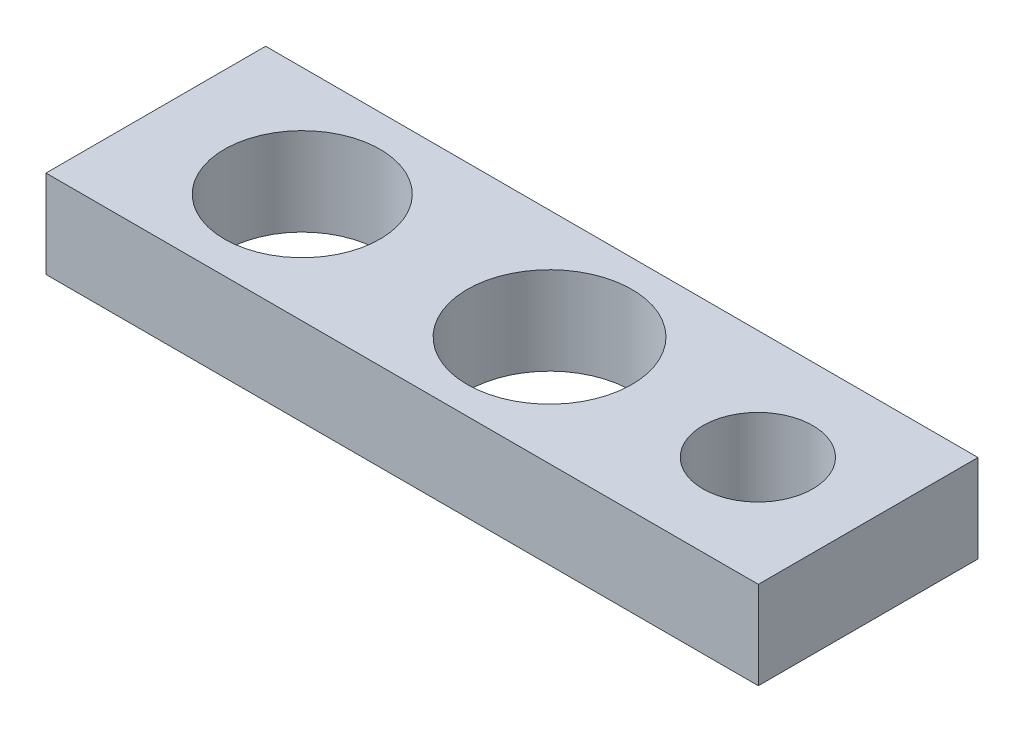
SolidWorks part; units mm, degrees
ref_plane "Front" through (0, 0, 0) normal (0, 0, 1) x (1, 0, 0)
ref_plane "Top" through (0, 0, 0) normal (0, 1, 0) x (1, 0, 0)
ref_plane "Right" through (0, 0, 0) normal (1, 0, 0) x (0, 0, -1)
sketch "Sketch1" plane through (0, 0, 0) normal (0, 1, 0) x (1, 0, 0)
  line L0 (0, 6.35) -> (38.1, 6.35)
  line L1 (0, 0) -> (38.1, 0)
  line L2 (0, 0) -> (0, 12.7)
  line L3 (0, 12.7) -> (38.1, 12.7)
  line L4 (38.1, 0) -> (38.1, 12.7)
  line L6 (0, 12.7) -> (-3.0858, 12.7)
  line L7 (0, 12.7) -> (0, 0)
  line L8 (0, 0) -> (-3.0858, 0)
  line L9 (-3.0858, 12.7) -> (-3.0858, 0)
  circle A0 centre (5.3798, 6.35) radius 4.5
  circle A2 centre (31.7225, 6.35) radius 3.175
  circle A3 centre (19.6779, 6.35) radius 4.7625
  dimension "D1" = 12.7
  dimension "D2" = 38.1
extrude "Boss-Extrude1" add sketch "Sketch1" along normal blind 5.08 contours A3 L0 A0 L2 L1 L4 A2 | A3 L0 A2 L4 L3 L2 A0 | L7 L6 L9 L8 region at (31.7225, 0, -9.9113) region at (36.4987, 0, -5.9637)
